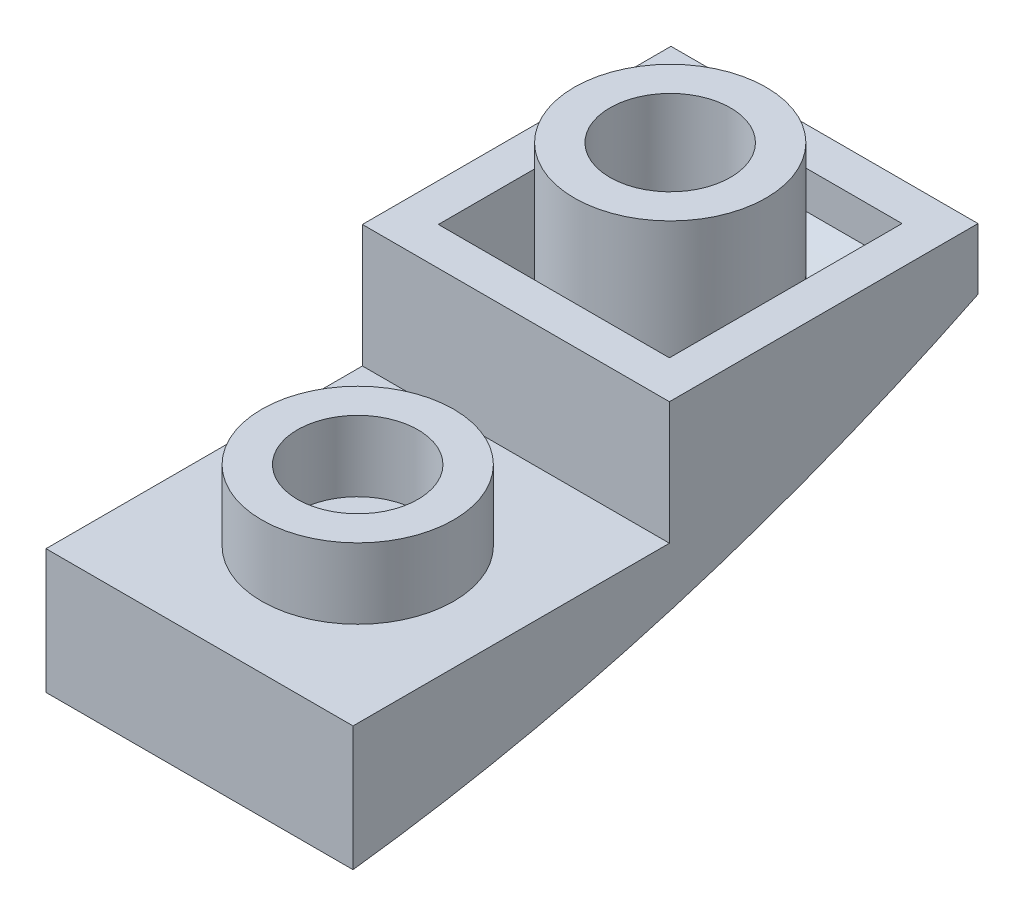
SolidWorks part; units mm, degrees
ref_plane "Front Plane" through (0, 0, 0) normal (0, 0, 1) x (1, 0, 0)
ref_plane "Top Plane" through (0, 0, 0) normal (0, 1, 0) x (1, 0, 0)
ref_plane "Right Plane" through (0, 0, 0) normal (1, 0, 0) x (0, 0, -1)
sketch "Sketch1" plane through (0, 0, 0) normal (1, 0, 0) x (0, 0, -1)
  line L0 (22.03, -44.8852) -> (22.03, -43.3202)
  line L1 (22.03, -43.3202) -> (14.15, -43.3202)
  line L2 (14.15, -43.3202) -> (14.15, -46.4502)
  line L3 (14.15, -46.4502) -> (6.07, -46.4502)
  line L4 (6.07, -46.4502) -> (6.07, -49.6302)
  arc A0 (6.07, -49.6302) -> (22.03, -44.8852) centre (0, 0) ccw
  dimension "D1" = 50
  dimension "D2" = 1.565
  dimension "D3" = 7.88
  dimension "D4" = 3.13
  dimension "D5" = 8.08
  dimension "D6" = 3.18
extrude "Boss-Extrude1" add sketch "Sketch1" against normal blind 7.84
shell "Shell1" thickness 0.97 removed face at (-3.92, -43.3202, -18.09)
ref_plane "Plane1" through (0, -41.5202, 0) normal (0, 1, 0) x (1, 0, 0)
sketch "Sketch2" plane through (0, -41.5202, 0) normal (0, 1, 0) x (1, 0, 0)
  line L0 (0, 22.03) -> (0, 14.15) construction
  line L1 (-7.84, 14.15) -> (0, 14.15) construction
  circle A0 centre (-3.92, 18.09) radius 1.54
  circle A1 centre (-3.92, 18.09) radius 2.45
  dimension "D2" = 3.94
  dimension "D3" = 4.9
  dimension "D4" = 3.08
  dimension "D1" = 3.92
extrude "Boss-Extrude2" add sketch "Sketch2" against normal up to surface (4.6322 mm away) up to face at (-3.92, -45.507, -18.1093)
sketch "Sketch3" plane through (0, -46.4502, 0) normal (0, 1, 0) x (1, 0, 0)
  line L0 (0, 14.15) -> (0, 6.07) construction
  line L2 (-7.84, 6.07) -> (0, 6.07) construction
  circle A0 centre (-3.92, 10.11) radius 2.45
  circle A1 centre (-3.92, 10.11) radius 1.54
  dimension "D1" = 3.92
  dimension "D3" = 4.9
  dimension "D4" = 3.08
  dimension "D2" = 4.04
extrude "Boss-Extrude3" add sketch "Sketch3" along normal blind 1.8
